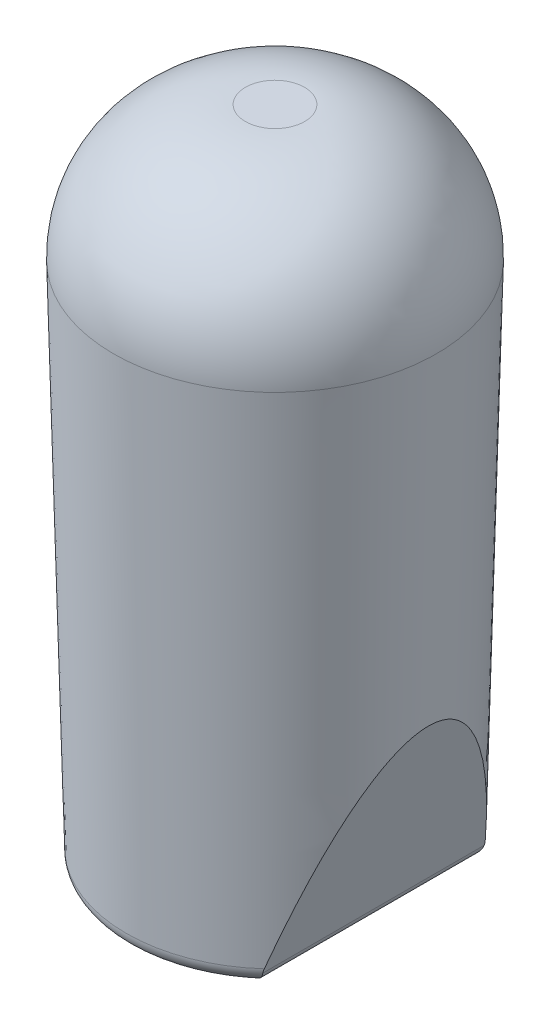
SolidWorks part; units mm, degrees
material "PVC Rígido"
ref_plane "Plano frontal" through (0, 0, 0) normal (0, 0, 1) x (1, 0, 0)
ref_plane "Plano superior" through (0, 0, 0) normal (0, 1, 0) x (1, 0, 0)
ref_plane "Plano direito" through (0, 0, 0) normal (1, 0, 0) x (0, 0, -1)
sketch "Esboço1" plane through (0, 0, 0) normal (0, 0, 1) x (1, 0, 0)
  line L0 (0, 0) -> (0, 40)
  line L1 (10, 40) -> (9, 0)
  line L2 (9, 0) -> (0, 0)
  line L3 (0, 40) -> (10, 40)
  dimension "D1" = 9
  dimension "D3" = 10
  dimension "D2" = 40
revolve "Revolução1" add sketch "Esboço1" angle 360 about L0
fillet "Filete1" radius 8 1 edges at (0, 40, -10)
sketch "Esboço2" plane through (0, 0, 0) normal (0, 0, 1) x (1, 0, 0)
  line L0 (-9.3, 12) -> (-5.7609, 0)
  line L1 (-9, 0) -> (9, 0) construction
  line L2 (-9.795, 31.8001) -> (-9, 0) construction
  dimension "D1" = 15
  dimension "D2" = 12
extrude "Corte-extrusão1" cut sketch "Esboço2" along normal through all and the other way through all flip side to cut
mirror "Espelhar1" about plane through (0, 0, 0) normal (1, 0, 0) of "Corte-extrusão1"
fillet "Filete2" radius 1 4 edges at (5.7609, 0, 0) (-5.7609, 0, 0) (0, 0, -9) (0, 0, 9)
sketch "Esboço3" plane through (0, 0, 0) normal (0, -1, 0) x (1, 0, 0)
  line L1 (2.38, 7) -> (-2.38, 7)
  line L2 (2.38, 7) -> (2.38, -7)
  line L3 (2.38, -7) -> (-2.38, -7)
  line L4 (-2.38, 7) -> (-2.38, -7)
  line L5 (2.38, 7) -> (-2.38, -7) construction
  line L6 (2.38, -7) -> (-2.38, 7) construction
  point P0 (0, 0)
  dimension "D1" = 14
  dimension "D2" = 4.76
extrude "Corte-extrusão2" cut sketch "Esboço3" against normal blind 25
